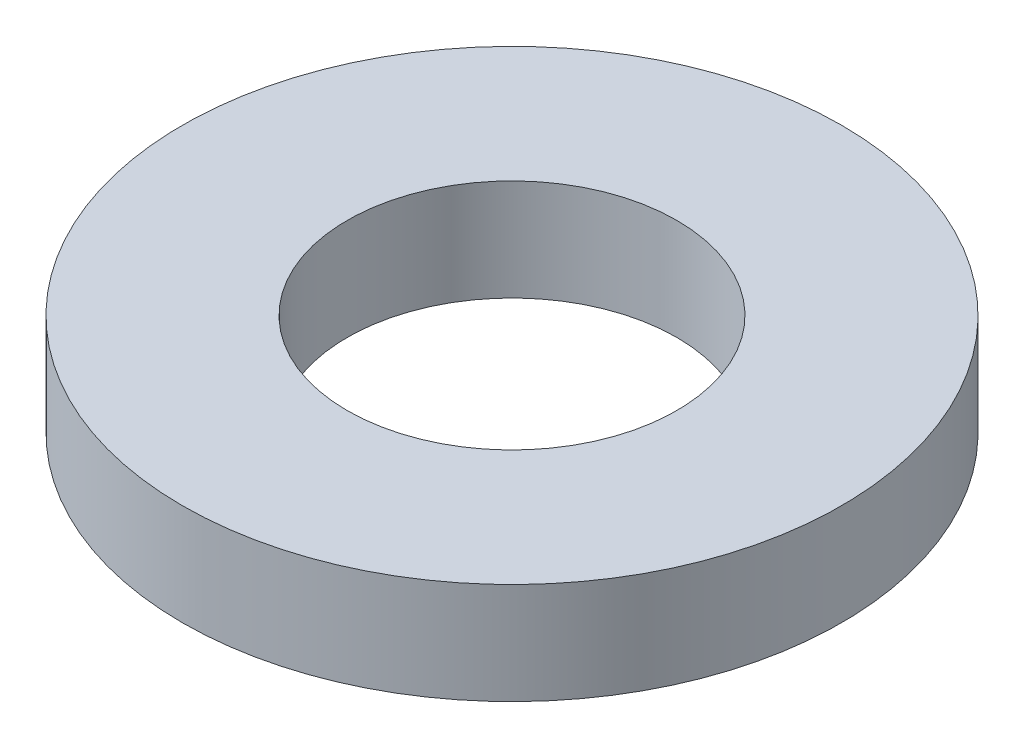
SolidWorks part; units mm, degrees
ref_plane "Front Plane" through (0, 0, 0) normal (0, 0, 1) x (1, 0, 0)
ref_plane "Top Plane" through (0, 0, 0) normal (0, 1, 0) x (1, 0, 0)
ref_plane "Right Plane" through (0, 0, 0) normal (1, 0, 0) x (0, 0, -1)
sketch "Sketch1" plane through (0, 0, 0) normal (0, 1, 0) x (1, 0, 0)
  circle A0 centre (0, 0) radius 65
  dimension "FLANGE_OD" = 130
extrude "Boss-Extrude1" add sketch "Sketch1" along normal blind 20
sketch "Sketch2" plane through (0, 0, 0) normal (0, 1, 0) x (1, 0, 0)
  circle A0 centre (0, 0) radius 32.5
  dimension "BORE_D" = 65
extrude "Cut-Extrude1" cut sketch "Sketch2" along normal through all
sketch "Sketch3" plane through (0, 20, 0) normal (0, 1, 0) x (1, 0, 0)
  circle A0 centre (0, 0) radius 18.4853 construction
  circle A1 centre (-18.4853, 0) radius 1.8384
  dimension "BOLT_D" = 3.6769
  dimension "BOLT_PCD" = 36.9706
extrude "Cut-Extrude2" cut sketch "Sketch3" against normal blind 18.0531 rebuild error yes
pattern_circular "CirPattern1" count 8 over 360 rebuild error yes
